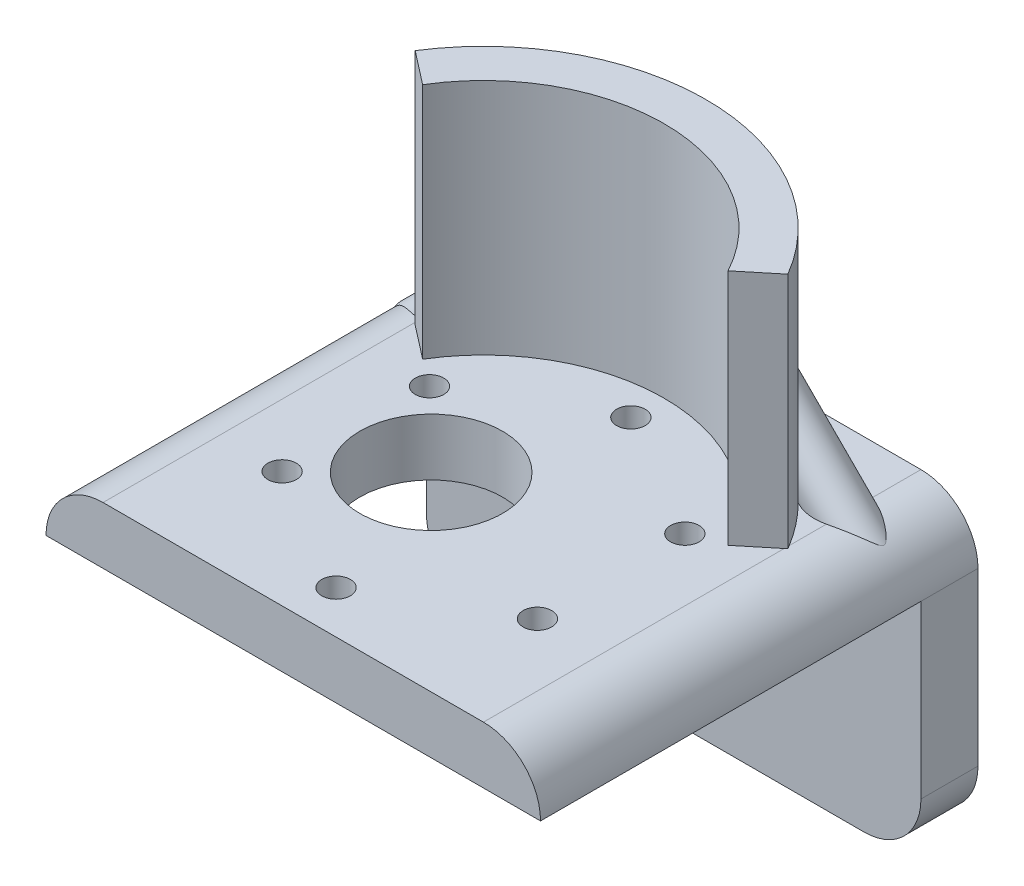
SolidWorks part; units mm, degrees
ref_plane "Front Plane" through (0, 0, 0) normal (0, 0, 1) x (1, 0, 0)
ref_plane "Top Plane" through (0, 0, 0) normal (0, 1, 0) x (1, 0, 0)
ref_plane "Right Plane" through (0, 0, 0) normal (1, 0, 0) x (0, 0, -1)
sketch "Sketch3" plane through (0, 0, 0) normal (0, 0, 1) x (1, 0, 0)
  line L0 (-20, 10.2406) -> (20, 10.2406)
  line L1 (26, 4.2406) -> (26, -13.7594)
  line L2 (20, -19.7594) -> (-20, -19.7594)
  line L3 (0, 19.985) -> (0, -19.985) construction
  line L4 (-26, 4.2406) -> (-26, -13.7594)
  arc A0 (20, 10.2406) -> (26, 4.2406) centre (20, 4.2406) cw
  arc A1 (26, -13.7594) -> (20, -19.7594) centre (20, -13.7594) cw
  arc A2 (-26, -13.7594) -> (-20, -19.7594) centre (-20, -13.7594) ccw
  arc A3 (-20, 10.2406) -> (-26, 4.2406) centre (-20, 4.2406) ccw
  point P12 (0, 0)
  point P14 (0, -19.7594)
  point P19 (0, 10.2406)
  dimension "D3" = 6
  dimension "D4" = 6
  dimension "D1" = 30
  dimension "D2" = 52
extrude "Boss-Extrude1" add sketch "Sketch3" along normal blind 6
sketch "Sketch4" plane through (0, 0, 6) normal (0, 0, 1) x (1, 0, 0)
  line L0 (-26, 4.2406) -> (26, 4.2406)
  line L1 (20, 10.2406) -> (-20, 10.2406)
  arc A0 (26, 4.2406) -> (20, 10.2406) centre (20, 4.2406) ccw
  arc A1 (-20, 10.2406) -> (-26, 4.2406) centre (-20, 4.2406) ccw
extrude "Boss-Extrude2" add sketch "Sketch4" along normal blind 40
sketch "Sketch9" plane through (0, 10.2406, 0) normal (0, 1, 0) x (1, 0, 0)
  line L0 (20, -46) -> (-20, -46) construction
  circle A0 centre (0, -26) radius 18.5
  circle A1 centre (0, -26) radius 17
  circle A2 centre (0, -10.5) radius 1.5
  circle A3 centre (13.4234, -18.25) radius 1.5
  circle A4 centre (13.4234, -33.75) radius 1.5
  circle A5 centre (0, -41.5) radius 1.5
  circle A6 centre (-13.4234, -33.75) radius 1.5
  circle A7 centre (-13.4234, -18.25) radius 1.5
  point P20 (0, -26)
  dimension "D1" = 37
  dimension "D3" = 34
  dimension "D4" = 3
  dimension "D2" = 20
  dimension "D5" = 6
extrude "Cut-Extrude1" cut sketch "Sketch9" against normal up to next contours A5 | A4 | A6 | A7 | A2 | A3 region at (13.4234, 10.2406, 18.25) region at (0, 10.2406, 10.5) region at (-13.4234, 10.2406, 18.25) region at (-13.4234, 10.2406, 33.75) region at (0, 10.2406, 41.5) region at (13.4234, 10.2406, 33.75)
sketch "Sketch10" plane through (0, 10.2406, 0) normal (0, 1, 0) x (1, 0, 0)
  line L0 (-19.5497, -26) -> (14.199, -26) construction
  circle A0 centre (-5.5, -26) radius 7.5
  point P0 (0, -26)
  dimension "D1" = 15
  dimension "D2" = 5.5
extrude "Cut-Extrude2" cut sketch "Sketch10" against normal up to next
sketch "Sketch11" plane through (0, 10.2406, 0) normal (0, 1, 0) x (1, 0, 0)
  line L5 (16.7554, -17.0414) -> (20.2096, -14.2045)
  line L6 (-16.2461, -16.1479) -> (-19.7428, -13.4388)
  arc A3 (-16.2461, -16.1479) -> (16.7554, -17.0414) centre (0, -26) cw
  arc A4 (-19.7428, -13.4388) -> (20.2096, -14.2045) centre (0, -26) cw
  dimension "D1" = 19
  dimension "D2" = 23.4
extrude "Boss-Extrude4" add sketch "Sketch11" along normal blind 25
ref_axis "Axis2" through (26, 10.2406, 0) along (0, 0, 1)
ref_plane "Plane1" through (7.8797, -7.8797, 0) normal (-0.7071, 0.7071, 0) x (0, 0, 1)
ref_axis "Axis3" through (-26, 10.2406, 6) along (0, 0, -1)
ref_plane "Plane2" through (-7.8797, -7.8797, 0) normal (0.7071, 0.7071, 0) x (0, 0, -1)
sketch "Sketch12" plane through (7.8797, -7.8797, 0) normal (-0.7071, 0.7071, 0) x (0, 0, 1)
  circle A0 centre (7.5748, 20.5948) radius 2.5
  dimension "D1" = 5
extrude "Boss-Extrude5" add sketch "Sketch12" along normal up to next
sketch "Sketch14" plane through (-7.8797, -7.8797, 0) normal (0.7071, 0.7071, 0) x (0, 0, -1)
  circle A0 centre (-10.2833, 20.7805) radius 2.5
  dimension "D1" = 5
extrude "Boss-Extrude6" add sketch "Sketch14" along normal up to next
